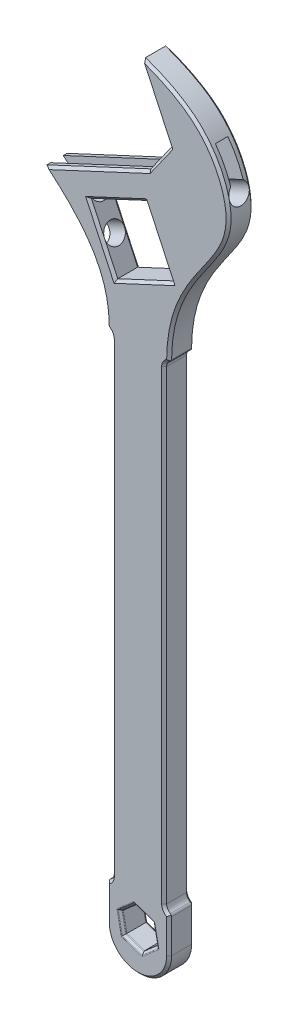
SolidWorks part; units mm, degrees
material "Alloy Steel"
ref_plane "Front Plane" through (0, 0, 0) normal (0, 0, 1) x (1, 0, 0)
ref_plane "Top Plane" through (0, 0, 0) normal (0, 1, 0) x (1, 0, 0)
ref_plane "Right Plane" through (0, 0, 0) normal (1, 0, 0) x (0, 0, -1)
sketch "Sketch1" plane through (0, 0, 0) normal (0, 0, 1) x (1, 0, 0)
  line L0 (236.808, 243.3013) -> (-25, 243.3013) construction
  line L1 (-39.7647, 103.8358) -> (86.8817, 103.8358) construction
  line L2 (0, 7.6716) -> (0, -6.519)
  line L3 (0, 200) -> (25, 200) construction
  line L4 (25, 7.6716) -> (25, -6.519)
  line L5 (-25, 243.3013) -> (0, 200) construction
  line L6 (0, 200) -> (0, 354.8084) construction
  line L7 (-25, 243.3013) -> (16.6876, 262.7405)
  line L8 (25.9975, 275.9088) -> (14.5868, 300.3791)
  line L9 (23.0392, 282.253) -> (36.1807, 288.3809) construction
  line L10 (36.1807, 288.3809) -> (48.8592, 261.1917) construction
  line L11 (0, 217.3205) -> (0, 177.3205) construction
  line L12 (-78.6231, 288.2964) -> (28.6231, 198.3061) construction
  line L13 (25, 190.1644) -> (25, 227.3435) construction
  line L14 (106.1716, 267.045) -> (-76.9979, 333.7133) construction
  line L15 (-7.1792, 240.5775) -> (3.3863, 217.9198)
  line L16 (-7.1792, 240.5775) -> (15.4785, 251.1429)
  line L17 (3.3863, 217.9198) -> (26.044, 228.4852)
  line L18 (15.4785, 251.1429) -> (26.044, 228.4852)
  line L19 (12.5, 34.821) -> (12.5, -26.7935) construction
  line L20 (25.9975, 275.9088) -> (16.6876, 262.7405)
  line L21 (2, 10.5) -> (2, 197.1716)
  line L23 (13.9587, -10.3624) -> (19.6054, -5.418)
  line L24 (19.6054, -5.418) -> (18.1467, 1.9445)
  line L25 (23, 10.5) -> (23, 197.1716)
  line L26 (18.1467, 1.9445) -> (11.0413, 4.3624)
  line L27 (11.0413, 4.3624) -> (5.3946, -0.582)
  line L28 (5.3946, -0.582) -> (6.8533, -7.9445)
  line L29 (6.8533, -7.9445) -> (13.9587, -10.3624)
  arc A0 (0, -6.519) -> (25, -6.519) centre (12.5, -6.519) ccw
  arc A1 (23, 10.5) -> (25, 7.6716) centre (26, 10.5) ccw
  arc A2 (2, 10.5) -> (0, 7.6716) centre (-1, 10.5) cw
  circle A3 centre (12.5, -3) radius 6.5 construction
  arc A5 (2, 197.1716) -> (0, 200) centre (-1, 197.1716) ccw
  arc A6 (23, 197.1716) -> (25, 200) centre (26, 197.1716) cw
  spline S0 degree 3 poles (0, 200) (0, 216.6667) (-7.1256, 228.3029) (-25, 243.3013) knots 0 0 0 0 1 1 1 1
  spline S1 degree 3 poles (14.5868, 300.3791) (20.8514, 298.099) (40.2278, 290.0553) (59.4408, 245.8815) (25, 233.3333) (25, 200) knots 0 0 0 0 0.205207 0.454414 1 1 1 1
  point P3 (23.5505, 198.9036)
  dimension "D11" = 50
  dimension "D12" = 70
  dimension "D14" = 100
  dimension "D15" = 20
  dimension "D7" = 122.6008
  dimension "D20" = 12.5
  dimension "D21" = 3
  dimension "D22" = 3
  dimension "D27" = 3
  dimension "D28" = 10.5
  dimension "D25" = 6.519
  dimension "D3" = 30
  dimension "D4" = 50
  dimension "D5" = 25
  dimension "D6" = 8
  dimension "D8" = 14.5
  dimension "D9" = 30
  dimension "D10" = 20
  dimension "D13" = 20
  dimension "D16" = 45
  dimension "D17" = 10
  dimension "D18" = 15
  dimension "D19" = 25
  dimension "D23" = 29.74
  dimension "D24" = 27
  dimension "D26" = 2
  dimension "D29" = 200
  dimension "D30" = 13
  dimension "D31" = 3
  dimension "D32" = 5.6467
extrude "Boss-Extrude1" add sketch "Sketch1" along normal mid plane 10
sketch "Sketch4" plane through (108.9073, 50.7843, 0) normal (-0.9063, -0.4226, 0) x (0, 0, 1)
  line L0 (5, 221.0713) -> (-5, 196.0713) construction
  circle A0 centre (0, 208.5713) radius 4
  dimension "D1" = 8
extrude "Cut-Extrude1" cut sketch "Sketch4" against normal blind 5 and the other way blind 70
sketch "Sketch5" plane through (127.0334, 59.2367, 0) normal (-0.9063, -0.4226, 0) x (0, 0, 1)
  line L0 (0, 266.0713) -> (0, 220.8329) construction
  line L1 (5, 266.0713) -> (-5, 266.0713) construction
  line L2 (5, 231.0713) -> (-5, 231.0713) construction
  line L3 (2.5, 239.0713) -> (-2.5, 239.0713)
  line L4 (2.5, 239.0713) -> (2.5, 224.0713)
  line L5 (2.5, 224.0713) -> (-2.5, 224.0713)
  line L6 (-2.5, 239.0713) -> (-2.5, 224.0713)
  circle A0 centre (0, 222.5713) radius 4
  dimension "D1" = 8
  dimension "D3" = 8.5
  dimension "D2" = 5
  dimension "D4" = 15
  dimension "D5" = 8
extrude "Cut-Extrude2" cut sketch "Sketch5" against normal mid plane 175 contours L4 L5 L6 L3 | A0
chamfer "Chamfer1" distance 1 angle 45 47 edges at (-1.8965, 229.2486, -5) (14.7151, 223.2025, -5) (20.7612, 239.8141, -5) (4.1496, 245.8602, -5) (4.1496, 245.8602, 5) (-1.8965, 229.2486, 5) (14.7151, 223.2025, 5) (20.7612, 239.8141, 5) (21.3426, 269.3247, -5) (-4.1562, 253.0209, -5) (1.4495, 198.9036, -5) (1.4495, 8.7679, -5) (2, 103.8358, -5) (23.5505, 8.7679, -5) (23.5505, 198.9036, -5) (23, 103.8358, -5) (0, 0.5763, -5) (12.5, -19.019, -5) (25, 0.5763, -5) (0, 0.5763, 5) (25, 0.5763, 5) (12.5, -19.019, 5) (23.5505, 8.7679, 5) (23.5505, 198.9036, 5) (23, 103.8358, 5) (21.3426, 269.3247, 5) (-4.1562, 253.0209, 5) (1.4495, 198.9036, 5) (1.4495, 8.7679, 5) (2, 103.8358, 5) (6.1239, -4.2633, -5) (8.218, 1.8902, -5) (14.594, 3.1535, -5) (18.8761, -1.7367, -5) (16.7821, -7.8902, -5) (10.406, -9.1535, -5) (20.2922, 288.144, -5) (10.406, -9.1535, 5) (6.1239, -4.2633, 5) (8.218, 1.8902, 5) (14.594, 3.1535, 5) (18.8761, -1.7367, 5) (16.7821, -7.8902, 5)
fillet "Fillet1" radius 1 4 edges at (0, 7.6716, 0) (25, 7.6716, 0)
fillet "Fillet3" radius 0.5 5 edges at (10.406, -9.1535, 4) (16.7821, -7.8902, 4) (14.594, 3.1535, 4) (8.218, 1.8902, 4) (6.1239, -4.2633, 4)
fillet "Fillet4" radius 0.5 6 edges at (16.7821, -7.8902, -4) (10.406, -9.1535, -4) (6.1239, -4.2633, -4) (8.218, 1.8902, -4) (14.594, 3.1535, -4) (18.8761, -1.7367, -4)
fillet "Fillet5" radius 0.5 12 edges at (10.0838, -10.1002, 5) (5.143, -4.4576, -5) (10.0838, -10.1002, -5) (17.4408, -8.6425, -5) (19.857, -1.5424, -5) (14.9162, 4.1002, -5) (7.5592, 2.6425, -5) (5.143, -4.4576, 5) (7.5592, 2.6425, 5) (14.9162, 4.1002, 5) (19.857, -1.5424, 5) (17.4408, -8.6425, 5)
